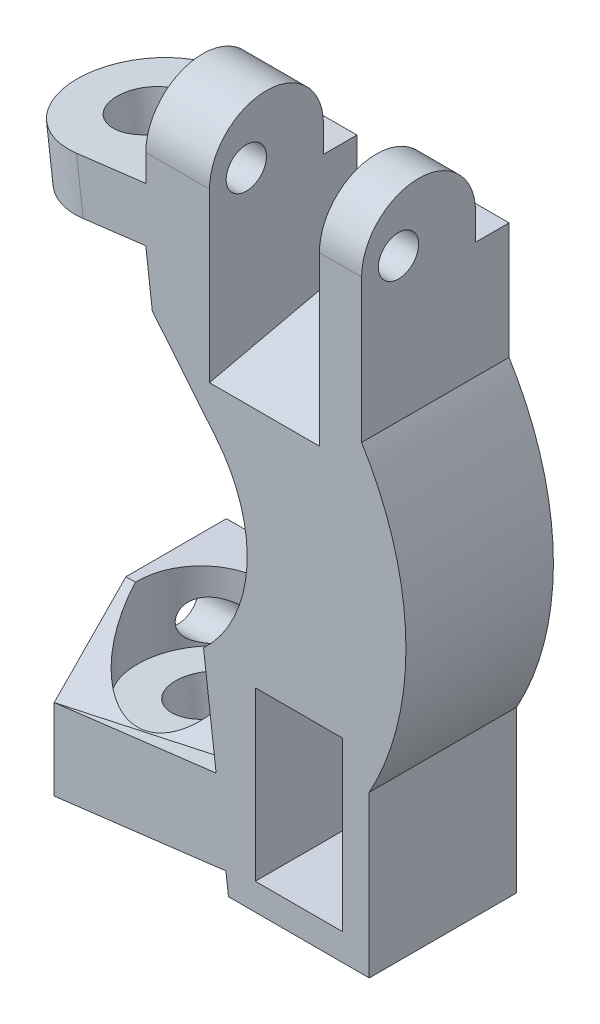
SolidWorks part; units mm, degrees
ref_plane "Front Plane" through (0, 0, 0) normal (0, 0, 1) x (1, 0, 0)
ref_plane "Top Plane" through (0, 0, 0) normal (0, 1, 0) x (1, 0, 0)
ref_plane "Right Plane" through (0, 0, 0) normal (1, 0, 0) x (0, 0, -1)
sketch "Sketch1" plane through (0, 0, 0) normal (0, 0, 1) x (1, 0, 0)
  line L0 (0, 0) -> (-10.5, 0)
  line L1 (-23.5, 0) -> (-10.6931, 1.5725)
  line L2 (0, 0) -> (0, 12)
  line L3 (-0.5696, 34.3109) -> (-0.5696, 43)
  line L4 (-0.5696, 43) -> (-16.6696, 43)
  line L5 (-16.6696, 38.97) -> (-16.1821, 34.9998)
  line L6 (-16.1821, 34.9998) -> (-11.433, 29.1949)
  line L7 (-5.25, 0) -> (-5.25, 18.4215) construction
  line L8 (-8.5, 14.5) -> (-2, 14.5)
  line L9 (-8.5, 14.5) -> (-8.5, 2)
  line L10 (-8.5, 2) -> (-2, 2)
  line L11 (-2, 14.5) -> (-2, 2)
  line L12 (-10.5, 0) -> (-10.6931, 1.5725)
  line L13 (-23.5, 6.0451) -> (-11.4243, 7.5278)
  line L14 (-23.5, 6.0451) -> (-23.5, 0)
  line L15 (-17.4621, 6.7864) -> (-21.8308, 42.3663) construction
  line L16 (-16.6696, 38.97) -> (-21.3433, 38.3961)
  line L17 (-21.3433, 38.3961) -> (-21.8308, 42.3663)
  line L18 (-21.8308, 42.3663) -> (-16.6696, 43)
  line L19 (-11.4243, 7.5278) -> (-12.3599, 15.1476)
  arc A0 (-12.3599, 15.1476) -> (-11.433, 29.1949) centre (-19.4121, 22.6672) ccw
  arc A1 (0, 12) -> (-0.5696, 34.3109) centre (-19.4121, 22.6672) ccw
  point P17 (-5.25, 2)
  point P23 (-19.4121, 22.6672)
  dimension "D3" = 10.5
  dimension "D6" = 97
  dimension "D1" = 16.1
  dimension "D2" = 43
  dimension "D4" = 6.5
  dimension "D5" = 12.5
  dimension "D7" = 7
  dimension "D8" = 16
  dimension "D9" = 15
  dimension "D10" = 6
  dimension "D11" = 2
  dimension "D12" = 5.2
  dimension "D13" = 4
  dimension "D14" = 4
  dimension "D15" = 12
  dimension "D16" = 7.5
extrude "Main Base" add sketch "Sketch1" along normal blind 11
sketch "Sketch2" plane through (-0.5696, 0, 0) normal (1, 0, 0) x (0, 0, -1)
  line L0 (-11, 43) -> (-11, 45)
  line L1 (-2.5, 43) -> (-2.5, 45)
  line L2 (-11, 0) -> (0, 0) construction
  line L5 (-11, 43) -> (-2.5, 43)
  arc A0 (-2.5, 45) -> (-11, 45) centre (-6.75, 45) ccw
  dimension "D2" = 8.5
  dimension "D1" = 45
extrude "Top Link Holes" add sketch "Sketch2" against normal up to vertex (16.1 mm away) up to point (-16.6696, 43, 11)
sketch "Sketch3" plane through (-5.4489, 44.3777, 0) normal (-0.1219, 0.9925, 0) x (0.9925, 0.1219, 0)
  line L0 (-16.5049, -11) -> (-16.5049, 0) construction
  line L1 (-11.3049, 0) -> (-16.5049, 0) construction
  line L2 (-16.5049, 0) -> (-16.5049, -11)
  arc A0 (-16.5049, 0) -> (-16.5049, -11) centre (-16.5049, -5.5) ccw
extrude "Steering Mount Boss" add sketch "Sketch3" against normal up to surface (4 mm away) up to face at (-19.0064, 38.683, 5.5)
ref_plane "Plane2" through (-7.8196, 0, 0) normal (1, 0, 0) x (0, 0, -1)
sketch "Sketch5" plane through (-7.8196, 0, 0) normal (1, 0, 0) x (0, 0, -1)
  line L0 (-11, 32.5) -> (0, 35)
  line L1 (-11, 34.3109) -> (-11, 45) construction
  line L2 (0, 34.3109) -> (0, 43) construction
  line L3 (0, 43) -> (-2.5, 43)
  line L4 (-2.5, 43) -> (-2.5, 45)
  line L5 (0, 35) -> (0, 43)
  line L8 (-11, 32.5) -> (-11, 45)
  line L9 (-11, 0) -> (0, 0) construction
  arc A0 (-2.5, 45) -> (-11, 45) centre (-6.75, 45) ccw
  dimension "D1" = 35
  dimension "D2" = 32.5
extrude "Cut for Link" cut sketch "Sketch5" against normal mid plane 8.2
sketch "Sketch12" plane through (-23.5, 0, 0) normal (-1, 0, 0) x (0, 0, 1)
  line L0 (11, 0) -> (0, 0) construction
  line L1 (11, 6.0451) -> (11, 0) construction
  line L2 (11, 6.0451) -> (0, 6.0451) construction
  line L3 (0, 6.0451) -> (0, 0) construction
  line L4 (11, 6.0451) -> (0, 6.0451)
  line L5 (0, 6.0451) -> (0, 4.854)
  line L6 (3.3042, 4.4) -> (15.7082, 4.4) construction
  line L7 (5.65, 11.5) -> (-1.85, 11.5)
  line L9 (5.65, 11.5) -> (11, 6.0451)
  line L10 (-1.85, 8) -> (-1.85, 11.5)
  arc A1 (-1.85, 8) -> (0, 4.854) centre (1.75, 8) ccw
  point P21 (-1.3532, 6.1752)
  dimension "D5" = 3.6
  dimension "D1" = 8
  dimension "D2" = 9.25
  dimension "D3" = 11.5
  dimension "D4" = 7.5
extrude "Boss-Extrude6" add sketch "Sketch12" against normal up to surface (11.588 mm away) up to face at (-11.8921, 11.3377, 5.5)
sketch "Sketch4" plane through (-5.4489, 44.3777, 0) normal (-0.1219, 0.9925, 0) x (0.9925, 0.1219, 0)
  circle A0 centre (-16.5049, -5.5) radius 2.5
  arc A1 (-16.5049, 0) -> (-16.5049, -11) centre (-16.5049, -5.5) ccw construction
  dimension "D1" = 5
extrude "Steering mount holes" cut sketch "Sketch4" against normal up to surface (41.8471 mm away) up to face at (-17.0965, 0.7862, 5.5)
ref_axis "Axis1" through (-15.1784, -11.8133, 5.5) along (-0.1219, 0.9925, 0)
sketch "Sketch13" plane through (-23.5, 0, 0) normal (-1, 0, 0) x (0, 0, 1)
  circle A0 centre (1.75, 8) radius 1.5
  arc A1 (-1.85, 8) -> (0, 4.854) centre (1.75, 8) ccw construction
  dimension "D1" = 3
extrude "Cut-Extrude8" cut sketch "Sketch13" against normal up to surface (15 mm away) up to face at (-8.5, 8.25, 5.5)
sketch "Sketch14" plane through (0, 11.5, 0) normal (0, 1, 0) x (1, 0, 0)
  circle A0 centre (-18.0409, -5.5) radius 4.75
  ellipse E1 centre (-18.0409, -5.5) end of major axis (-20.5597, -5.5) minor radius 2.5 (-15.5267, -5.65) -> (-20.5551, -5.65) ccw construction
  dimension "D1" = 9.5
extrude "Cut-Extrude9" cut sketch "Sketch14" against normal up to surface (4.7846 mm away) up to face at (-15.4495, 7.0335, 10.5153)
sketch "Sketch15" plane through (-0.5696, 0, 0) normal (1, 0, 0) x (0, 0, -1)
  line L0 (-11, 34.3109) -> (0, 34.3109) construction
  circle A0 centre (-8.25, 45) radius 1.5
  arc A1 (-2.5, 45) -> (-11, 45) centre (-6.75, 45) ccw construction
  point P8 (-6.75, 49.25)
  dimension "D1" = 3
  dimension "D2" = 10.6891
  dimension "D3" = 1.5
extrude "Cut-Extrude10" cut sketch "Sketch15" against normal up to surface (16.1 mm away) up to face at (-16.6696, 45.0625, 6.75)
